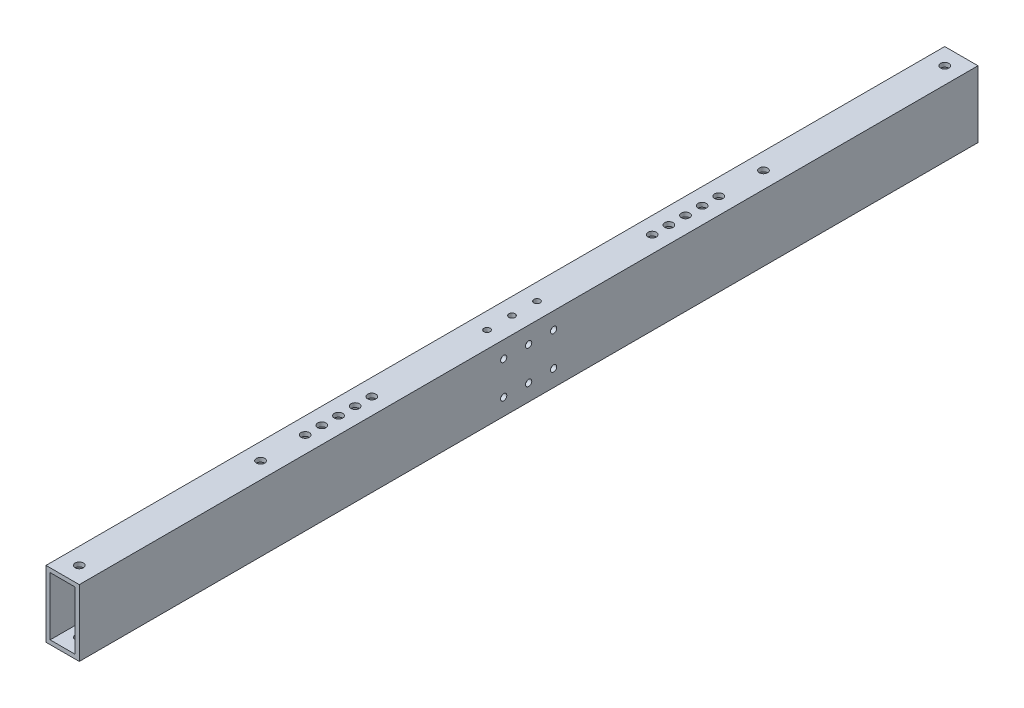
SolidWorks part; units mm, degrees
ref_plane "Front Plane" through (0, 0, 0) normal (0, 0, 1) x (1, 0, 0)
ref_plane "Top Plane" through (0, 0, 0) normal (0, 1, 0) x (1, 0, 0)
ref_plane "Right Plane" through (0, 0, 0) normal (1, 0, 0) x (0, 0, -1)
sketch "Sketch1" plane through (0, 0, 0) normal (0, 0, 1) x (1, 0, 0)
  line L0 (-9.525, 22.225) -> (9.525, 22.225)
  line L1 (-12.7, -25.4) -> (12.7, -25.4)
  line L2 (-12.7, -25.4) -> (-12.7, 25.4)
  line L3 (-12.7, 25.4) -> (12.7, 25.4)
  line L4 (12.7, -25.4) -> (12.7, 25.4)
  line L5 (-12.7, -25.4) -> (12.7, 25.4) construction
  line L6 (-12.7, 25.4) -> (12.7, -25.4) construction
  line L7 (9.525, -22.225) -> (9.525, 22.225)
  line L8 (-9.525, -22.225) -> (9.525, -22.225)
  line L9 (-9.525, -22.225) -> (-9.525, 22.225)
  point P0 (0, 0)
  dimension "D1" = 25.4
  dimension "D2" = 50.8
  dimension "D3" = 3.175
extrude "Boss-Extrude1" add sketch "Sketch1" along normal blind 685.8
sketch "Sketch2" plane through (0, 25.4, 0) normal (0, 1, 0) x (1, 0, 0)
  line L0 (0, -685.8) -> (0, 0) construction
  line L1 (12.7, -685.8) -> (-12.7, -685.8) construction
  line L2 (12.7, 0) -> (-12.7, 0) construction
  line L3 (-12.7, -342.9) -> (12.7, -342.9) construction
  line L4 (-12.7, -685.8) -> (-12.7, 0) construction
  line L5 (12.7, -685.8) -> (12.7, 0) construction
  circle A0 centre (0, -12.7) radius 3.175
  circle A1 centre (0, -151.0121) radius 3.175
  circle A2 centre (0, -534.7879) radius 3.175
  circle A3 centre (0, -673.1) radius 3.175
  circle A4 centre (0, -185.1063) radius 3.175
  circle A5 centre (0, -197.8063) radius 3.175
  circle A6 centre (0, -210.5063) radius 3.175
  circle A7 centre (0, -223.2063) radius 3.175
  circle A8 centre (0, -235.9063) radius 3.175
  circle A9 centre (0, -449.8937) radius 3.175
  circle A10 centre (0, -462.5937) radius 3.175
  circle A11 centre (0, -475.2937) radius 3.175
  circle A12 centre (0, -487.9937) radius 3.175
  circle A13 centre (0, -500.6937) radius 3.175
  dimension "D1" = 12.7
  dimension "D4" = 6.35
  dimension "D3" = 138.3121
  dimension "D5" = 172.4063
  dimension "D2" = 2
  dimension "D6" = 5
extrude "Cut-Extrude1" cut sketch "Sketch2" against normal through all
sketch "Sketch3" plane through (12.7, 0, 0) normal (1, 0, 0) x (0, 0, -1)
  line L0 (-685.8, 0) -> (0, 0) construction
  line L1 (-685.8, -25.4) -> (-685.8, 25.4) construction
  line L2 (0, -25.4) -> (0, 25.4) construction
  line L3 (-342.9, 25.4) -> (-342.9, -25.4) construction
  line L4 (-685.8, 25.4) -> (0, 25.4) construction
  line L5 (-685.8, -25.4) -> (0, -25.4) construction
  line L6 (-361.95, -25.4) -> (-361.95, 25.4) construction
  circle A0 centre (-361.95, -12.7) radius 2.3813
  circle A1 centre (-342.9, -12.7) radius 2.3813
  circle A2 centre (-323.85, -12.7) radius 2.3813
  circle A3 centre (-323.85, 12.7) radius 2.3813
  circle A4 centre (-361.95, 12.7) radius 2.3813
  circle A5 centre (-342.9, 12.7) radius 2.3813
  dimension "D1" = 4.7625
  dimension "D4" = 4.7625
  dimension "D2" = 12.7
  dimension "D3" = 19.05
extrude "Cut-Extrude2" cut sketch "Sketch3" against normal blind 3.175
sketch "Sketch4" plane through (0, -25.4, 0) normal (0, -1, 0) x (-1, 0, 0)
  line L0 (0, -685.8) -> (0, 0) construction
  line L1 (12.7, -685.8) -> (-12.7, -685.8) construction
  line L2 (12.7, 0) -> (-12.7, 0) construction
  line L3 (-12.7, -342.9) -> (12.7, -342.9) construction
  line L4 (-12.7, -685.8) -> (-12.7, 0) construction
  line L5 (12.7, -685.8) -> (12.7, 0) construction
  circle A0 centre (0, -342.9) radius 2.3813
  circle A1 centre (0, -361.95) radius 2.3813
  circle A2 centre (0, -323.85) radius 2.3813
  dimension "D1" = 4.7625
  dimension "D2" = 4.7625
  dimension "D3" = 19.05
extrude "Cut-Extrude3" cut sketch "Sketch4" against normal through all
